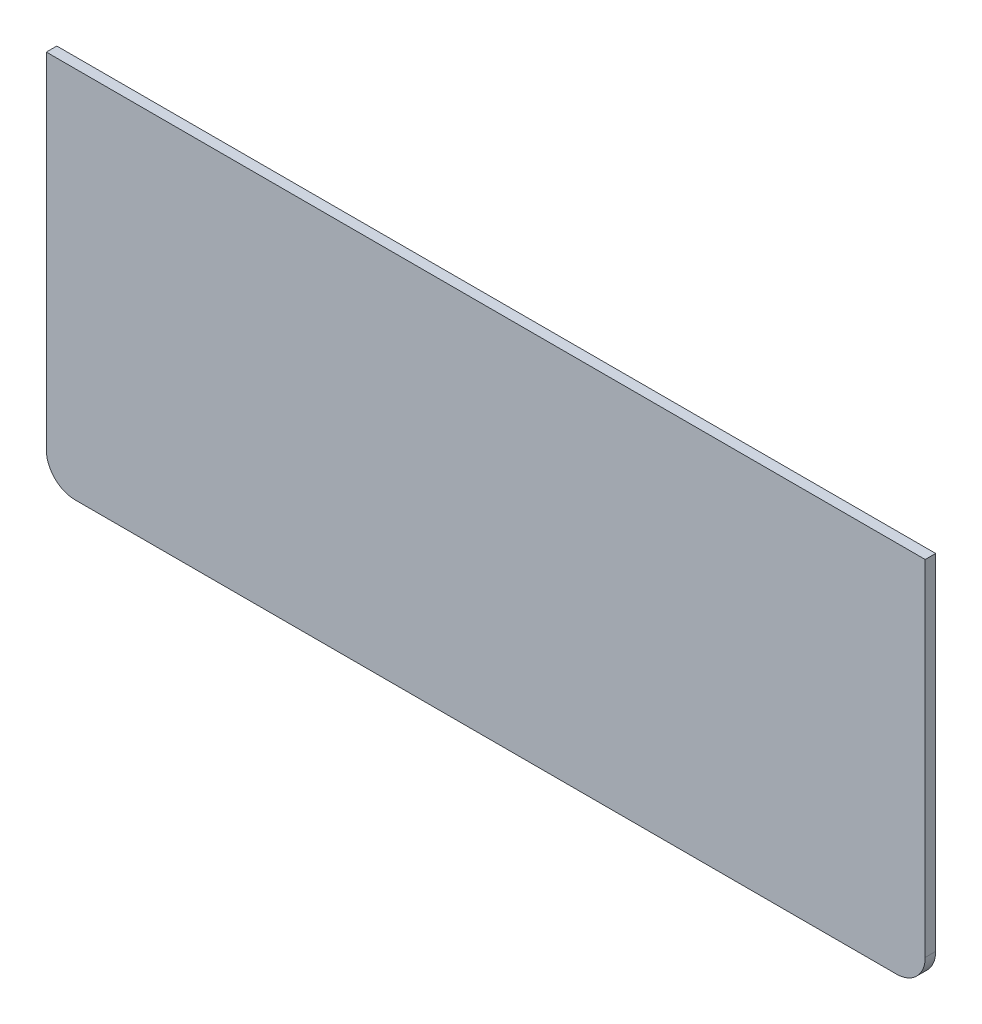
SolidWorks part; units mm, degrees
material "5052-H32"
ref_plane "Front Plane" through (0, 0, 0) normal (0, 0, 1) x (1, 0, 0)
ref_plane "Top Plane" through (0, 0, 0) normal (0, 1, 0) x (1, 0, 0)
ref_plane "Right Plane" through (0, 0, 0) normal (1, 0, 0) x (0, 0, -1)
sketch "Sketch2" plane through (0, 0, 0) normal (0, 0, 1) x (1, 0, 0)
  line L0 (-53.5866, 40.5355) -> (212.7634, 40.5355)
  line L1 (212.7634, 40.5355) -> (212.7634, -72.6395)
  line L2 (212.7634, -72.6395) -> (-53.5866, -72.6395)
  line L3 (-53.5866, -72.6395) -> (-53.5866, 40.5355)
  dimension "D1" = 113.175
  dimension "D2" = 266.35
extrude "Boss-Extrude1" add sketch "Sketch2" along normal blind 3.175
fillet "Fillet1" radius 8.7312 2 edges at (-53.5866, -72.6395, 1.5875) (212.7634, -72.6395, 1.5875)
equation "\"L\"= 500"
equation "\"W\"= 260"
equation "\"H\"= 110"
equation "\"Compartment Width\"= 90"
equation "\"T\"= 4.7625 * 2 / 3"
equation "\"Inside Fillet Radius\"= 5.55625"
equation "\"D1@Fillet1\"=\"Inside Fillet Radius\"+\"T\""
equation "\"D1@Sketch2\"=\"T\"+\"H\""
equation "\"D2@Sketch2\"=2*\"T\"+\"W\""
equation "\"D1@Boss-Extrude1\"=\"T\""
